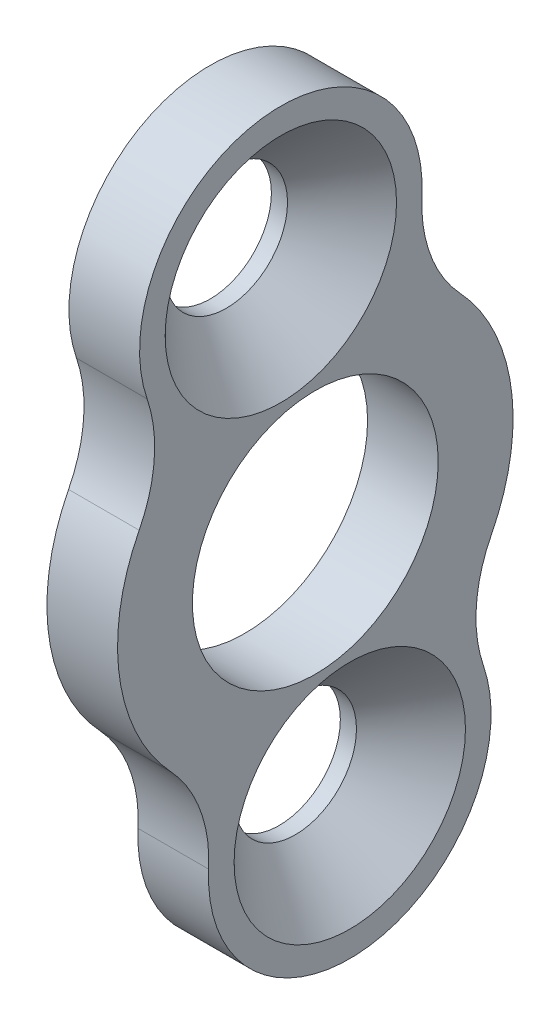
SolidWorks part; units mm, degrees
material "6061-T6 (SS)"
ref_plane "Front Plane" through (0, 0, 0) normal (0, 0, 1) x (1, 0, 0)
ref_plane "Top Plane" through (0, 0, 0) normal (0, 1, 0) x (1, 0, 0)
ref_plane "Right Plane" through (0, 0, 0) normal (1, 0, 0) x (0, 0, -1)
ref_axis "Axis1" through (31.75, 11.0234, 1.5492) along (1, 0, 0)
ref_axis "Axis2" through (31.75, -11.0234, -1.5492) along (1, 0, 0)
ref_plane "Plane1" through (0, 0, 0) normal (0, -0.1392, 0.9903) x (1, 0, 0)
sketch "Sketch1" plane through (0, 0, 0) normal (1, 0, 0) x (0, 0, -1)
  line L0 (1.5492, -11.0234) -> (-1.5492, 11.0234) construction
  circle A0 centre (0, 0) radius 5.5245
  circle A1 centre (0, 0) radius 4.7625 construction
  circle A2 centre (-1.5492, 11.0234) radius 2.75 construction
  circle A3 centre (1.5492, -11.0234) radius 2.75 construction
  arc A4 (-7.5607, 8.9777) -> (4.7932, 10.714) centre (-1.5492, 11.0234) cw
  arc A5 (4.7932, 10.714) -> (6.4958, 6.0693) centre (11.1357, 10.4045) ccw
  arc A6 (6.4958, 6.0693) -> (7.9171, -4.0437) centre (0, 0) cw
  arc A7 (7.9171, -4.0437) -> (7.5607, -8.9777) centre (13.5722, -6.9321) ccw
  arc A8 (7.5607, -8.9777) -> (-4.7932, -10.714) centre (1.5492, -11.0234) cw
  arc A9 (-4.7932, -10.714) -> (-6.4958, -6.0693) centre (-11.1357, -10.4045) ccw
  arc A10 (-6.4958, -6.0693) -> (-7.9171, 4.0437) centre (0, 0) cw
  arc A11 (-7.9171, 4.0437) -> (-7.5607, 8.9777) centre (-13.5722, 6.9321) ccw
  arc A12 (0.6891, 9.4258) -> (-3.2605, 8.8707) centre (-1.5492, 11.0234) ccw construction
  point P24 (-6.8112, 3.8686)
  point P25 (3.8369, 11.3645)
  point P26 (3.4557, 10.0456)
  point P27 (4.7566, 9.0359)
  dimension "D1" = 9.525
  dimension "D3" = 5.5
  dimension "D4" = 8.89
  dimension "D5" = 6.35
  dimension "D6" = 6.35
  dimension "D2" = 0.762
extrude "Boss-Extrude1" add sketch "Sketch1" along normal blind 3.175
hole_wizard "CSK for M5 Flat Head Machine Screw1" positions "Sketch2" profile "Sketch3" countersink size "M5" standard "ANSI Metric" end condition through all
sketch "Sketch2" plane through (3.175, 0, 0) normal (1, 0, 0) x (0, 0, -1)
  point P0 (-1.5492, 11.0234)
  point P3 (1.5492, -11.0234)
sketch "Sketch3" plane through (3.175, 11.0234, 1.5492) normal (0, 1, 0) x (0, 0, -1)
  line L0 (0, 0) -> (0, 3.175)
  line L1 (0, 3.175) -> (2.75, 3.175)
  line L2 (2.75, 3.175) -> (2.75, 2.45)
  line L3 (2.75, 2.45) -> (5.2, 0)
  line L5 (5.2, 0) -> (0, 0)
  line L6 (-2.75, 2.45) -> (-5.2, 0) construction
  line L11 (0, -6.35) -> (0, 107.95) construction
  dimension "Thru Hole Dia." = 5.5
  dimension "Thru Hole Depth" = 3.175
  dimension "Near C'Sink Dia." = 10.4
  dimension "Near C'Sink Angle" = 90
equation "\"D3@Sketch1\"=5.5mm"
